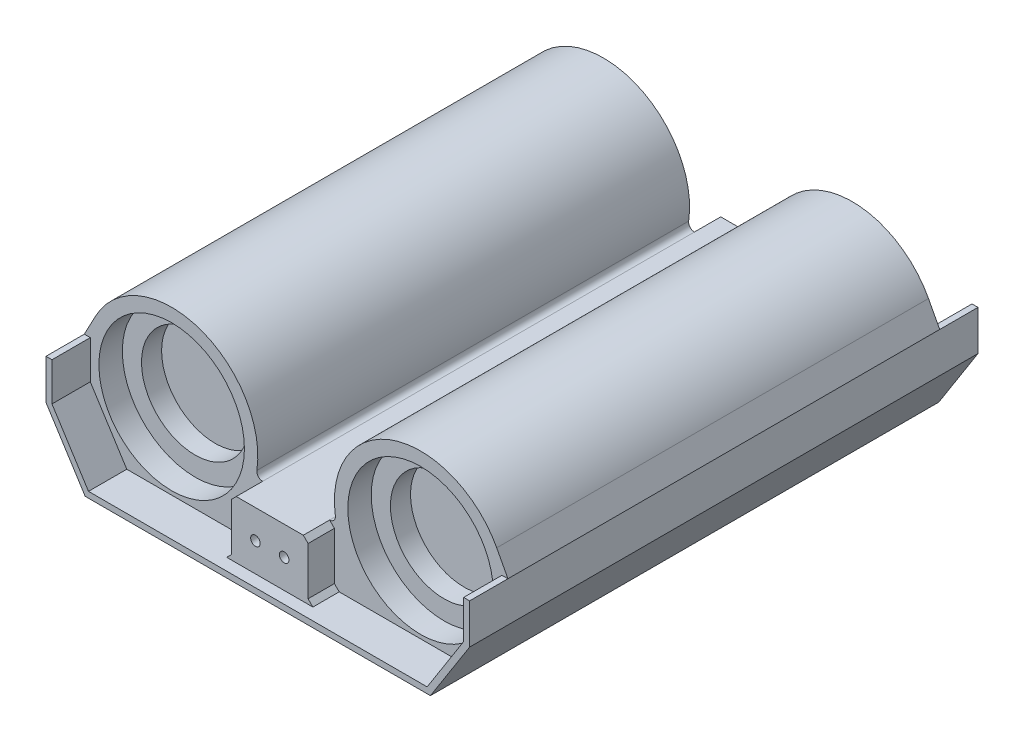
SolidWorks part; units mm, degrees
ref_plane "Front Plane" through (0, 0, 0) normal (0, 0, 1) x (1, 0, 0)
ref_plane "Top Plane" through (0, 0, 0) normal (0, 1, 0) x (1, 0, 0)
ref_plane "Right Plane" through (0, 0, 0) normal (1, 0, 0) x (0, 0, -1)
sketch "Sketch3" plane through (0, 0, 0) normal (0, 0, 1) x (1, 0, 0)
  line L0 (-7.5, -25) -> (7.5, -25) construction
  line L3 (-20, -10) -> (20, -10)
  line L4 (-20, -40) -> (-20, -10)
  line L5 (-20, -40) -> (20, -40)
  line L6 (20, -40) -> (20, -10)
  line L7 (0, -40) -> (0, -10) construction
  line L8 (0, -10) -> (0, 0) construction
  circle A2 centre (7.5, -25) radius 2.5
  circle A3 centre (-7.5, -25) radius 2.5
  point P11 (0, -25)
  dimension "D4" = 5
  dimension "D5" = 5
  dimension "D1" = 15
  dimension "D2" = 40
  dimension "D3" = 30
  dimension "D6" = 15
  dimension "D7" = 10
extrude "Boss-Extrude2" add sketch "Sketch3" along normal blind 6.25
sketch "Sketch4" plane through (0, 0, 6.25) normal (0, 0, 1) x (1, 0, 0)
  line L0 (20, -40) -> (20, -10) construction
  line L1 (-20, -40) -> (20, -40)
  line L2 (-20, -40) -> (-20, -33.75)
  line L3 (-20, -33.75) -> (20, -33.75)
  line L4 (20, -40) -> (20, -33.75)
  dimension "D1" = 6.25
extrude "Boss-Extrude3" add sketch "Sketch4" along normal blind 7.5
sketch "Sketch5" plane through (0, 0, 13.75) normal (0, 0, 1) x (1, 0, 0)
  line L1 (-20, -40) -> (-88.4287, -40)
  line L12 (-110.625, -10.9092) -> (-90.1451, -43.125)
  line L13 (0, -33.75) -> (0, -40) construction
  line L27 (-107.5, -10) -> (-88.4287, -40)
  line L29 (-107.5, 10) -> (-107.5, -10)
  line L30 (-107.5, 10) -> (-110.625, 10)
  line L31 (-110.625, 10) -> (-110.625, -10.9092)
  line L32 (110.625, 10) -> (110.625, -10.9092)
  line L33 (107.5, 10) -> (110.625, 10)
  line L34 (107.5, 10) -> (107.5, -10)
  line L35 (107.5, -10) -> (88.4287, -40)
  line L36 (110.625, -10.9092) -> (90.1451, -43.125)
  line L38 (20, -40) -> (88.4287, -40)
  line L39 (-90.1451, -43.125) -> (90.1451, -43.125)
  line L40 (-20, -40) -> (20, -40) construction
  line L41 (-20, -40) -> (20, -40)
  arc A1 (-104.9218, -10.3078) -> (-55, -40) centre (-65, 0) ccw construction
  arc A4 (104.9218, -10.3078) -> (55, -40) centre (65, 0) cw construction
  dimension "D3" = 3.125
  dimension "D2" = 3.125
  dimension "D4" = 3.125
  dimension "D7" = 20
  dimension "D1" = 10
  dimension "D5" = 42.5
  dimension "D6" = 50
  dimension "D8" = 65
extrude "Boss-Extrude4" add sketch "Sketch5" against normal blind 20
chamfer "Chamfer1" distance 2.5 angle 45 4 edges at (-20, -10, 3.125) (20, -10, 3.125) (-20, -40, 6.875) (20, -40, 6.875)
sketch "Sketch6" plane through (0, 0, 13.75) normal (0, 0, 1) x (1, 0, 0)
  line L0 (-110.625, 10) -> (-104.7676, 21.0604)
  line L1 (-90.1451, -43.125) -> (90.1451, -43.125) construction
  line L2 (-110.625, -10.9092) -> (-90.1451, -43.125) construction
  line L3 (-110.625, 10) -> (-110.625, -10.9092) construction
  line L4 (-90.1451, -43.125) -> (90.1451, -43.125)
  line L5 (-110.625, -10.9092) -> (-90.1451, -43.125)
  line L6 (-110.625, 10) -> (-110.625, -10.9092)
  line L7 (0, 0) -> (0, -43.125) construction
  line L9 (-65, 0) -> (0, 0) construction
  line L11 (17.5, -10) -> (-17.5, -10)
  line L15 (110.625, 10) -> (110.625, -10.9092)
  line L16 (110.625, -10.9092) -> (90.1451, -43.125)
  line L17 (110.625, 10) -> (104.7676, 21.0604)
  circle A1 centre (-65, 0) radius 38
  arc A3 (-20.4793, -6.5503) -> (-104.7676, 21.0604) centre (-65, 0) ccw
  arc A5 (-20.4793, -6.5503) -> (-17.5, -10) centre (-17.5, -6.9886) ccw
  arc A6 (20.4793, -6.5503) -> (17.5, -10) centre (17.5, -6.9886) cw
  arc A7 (20.4793, -6.5503) -> (104.7676, 21.0604) centre (65, 0) cw
  circle A8 centre (65, 0) radius 38
  point P26 (0, -10)
  dimension "D1" = 76
  dimension "D2" = 65
  dimension "D3" = 45
extrude "Boss-Extrude5" add sketch "Sketch6" along normal blind 12.25
sketch "Sketch8" plane through (0, 0, 26) normal (0, 0, 1) x (1, 0, 0)
  line L0 (-65, 0) -> (0, 0) construction
  line L1 (0, 0) -> (0, -43.125) construction
  line L2 (-90.1451, -43.125) -> (90.1451, -43.125) construction
  line L13 (-104.7676, 21.0604) -> (-110.625, 10)
  line L14 (-110.625, 10) -> (-110.625, -10.9092)
  line L15 (-110.625, -10.9092) -> (-90.1451, -43.125)
  line L16 (-90.1451, -43.125) -> (90.1451, -43.125)
  line L17 (90.1451, -43.125) -> (110.625, -10.9092)
  line L18 (110.625, -10.9092) -> (110.625, 10)
  line L19 (110.625, 10) -> (104.7676, 21.0604)
  line L21 (17.5, -10) -> (-17.5, -10)
  line L23 (-104.7676, 21.0604) -> (-110.625, 10)
  line L24 (-110.625, 10) -> (-110.625, -10.9092)
  line L25 (-110.625, -10.9092) -> (-90.1451, -43.125)
  line L26 (-90.1451, -43.125) -> (90.1451, -43.125)
  line L27 (90.1451, -43.125) -> (110.625, -10.9092)
  line L28 (110.625, -10.9092) -> (110.625, 10)
  line L29 (110.625, 10) -> (104.7676, 21.0604)
  line L31 (17.5, -10) -> (-17.5, -10)
  circle A0 centre (-65, 0) radius 28
  circle A1 centre (65, 0) radius 28
  arc A5 (-20.4793, -6.5503) -> (-104.7676, 21.0604) centre (-65, 0) ccw
  arc A6 (104.7676, 21.0604) -> (20.4793, -6.5503) centre (65, 0) ccw
  arc A7 (17.5, -10) -> (20.4793, -6.5503) centre (17.5, -6.9886) ccw
  arc A8 (-20.4793, -6.5503) -> (-17.5, -10) centre (-17.5, -6.9886) ccw
  arc A9 (-20.4793, -6.5503) -> (-104.7676, 21.0604) centre (-65, 0) ccw
  arc A10 (104.7676, 21.0604) -> (20.4793, -6.5503) centre (65, 0) ccw
  arc A11 (17.5, -10) -> (20.4793, -6.5503) centre (17.5, -6.9886) ccw
  arc A12 (-20.4793, -6.5503) -> (-17.5, -10) centre (-17.5, -6.9886) ccw
  dimension "D1" = 56
  dimension "D2" = 0
extrude "Boss-Extrude7" add sketch "Sketch8" along normal blind 10.5
sketch "Sketch9" plane through (0, 0, 36.5) normal (0, 0, 1) x (1, 0, 0)
  line L0 (0, 0) -> (0, -43.125) construction
  line L1 (-90.1451, -43.125) -> (90.1451, -43.125) construction
  circle A2 centre (65, 0) radius 31.125
  circle A3 centre (-65, 0) radius 31.125
  circle A4 centre (-65, 0) radius 31.125
  dimension "D1" = 3.125
extrude "Boss-Extrude8" add sketch "Sketch9" along normal blind 3.125
fillet "Fillet1" radius 4 2 edges at (33.875, 0, 36.5) (-33.875, 0, 36.5)
sketch "Sketch10" plane through (0, 0, 36.5) normal (0, 0, 1) x (1, 0, 0)
  line L10 (-104.7676, 21.0604) -> (-110.625, 10)
  line L11 (-110.625, 10) -> (-110.625, -10.9092)
  line L12 (-110.625, -10.9092) -> (-90.1451, -43.125)
  line L13 (-90.1451, -43.125) -> (90.1451, -43.125)
  line L14 (90.1451, -43.125) -> (110.625, -10.9092)
  line L15 (110.625, -10.9092) -> (110.625, 10)
  line L16 (110.625, 10) -> (104.7676, 21.0604)
  line L18 (17.5, -10) -> (-17.5, -10)
  line L20 (-104.7676, 21.0604) -> (-110.625, 10)
  line L21 (-110.625, 10) -> (-110.625, -10.9092)
  line L22 (-110.625, -10.9092) -> (-90.1451, -43.125)
  line L23 (-90.1451, -43.125) -> (-47.5, -43.125)
  line L24 (90.1451, -43.125) -> (110.625, -10.9092)
  line L25 (110.625, -10.9092) -> (110.625, 10)
  line L26 (110.625, 10) -> (104.7676, 21.0604)
  line L28 (17.5, -10) -> (-17.5, -10)
  line L30 (-47.5, -43.125) -> (-47.5, -40)
  line L31 (47.5, -43.125) -> (47.5, -40)
  line L32 (47.5, -43.125) -> (90.1451, -43.125)
  line L33 (47.5, -40) -> (88.4287, -40)
  line L40 (-102.006, 19.5978) -> (-107.5, 9.2236)
  line L41 (-107.5, 9.2236) -> (-107.5, -10)
  line L42 (-107.5, -10) -> (-88.4287, -40)
  line L43 (-88.4287, -40) -> (88.4287, -40)
  line L44 (88.4287, -40) -> (107.5, -10)
  line L45 (107.5, -10) -> (107.5, 9.2236)
  line L46 (107.5, 9.2236) -> (102.006, 19.5978)
  line L48 (17.5, -13.125) -> (-17.5, -13.125)
  line L50 (-102.006, 19.5978) -> (-107.5, 9.2236)
  line L51 (-107.5, 9.2236) -> (-107.5, -10)
  line L52 (-107.5, -10) -> (-88.4287, -40)
  line L53 (-88.4287, -40) -> (-47.5, -40)
  line L54 (88.4287, -40) -> (107.5, -10)
  line L55 (107.5, -10) -> (107.5, 9.2236)
  line L56 (107.5, 9.2236) -> (102.006, 19.5978)
  line L58 (17.5, -13.125) -> (-17.5, -13.125)
  arc A4 (-20.4793, -6.5503) -> (-104.7676, 21.0604) centre (-65, 0) ccw
  arc A5 (104.7676, 21.0604) -> (20.4793, -6.5503) centre (65, 0) ccw
  arc A6 (17.5, -10) -> (20.4793, -6.5503) centre (17.5, -6.9886) ccw
  arc A7 (-20.4793, -6.5503) -> (-17.5, -10) centre (-17.5, -6.9886) ccw
  arc A8 (-20.4793, -6.5503) -> (-104.7676, 21.0604) centre (-65, 0) ccw
  arc A9 (104.7676, 21.0604) -> (20.4793, -6.5503) centre (65, 0) ccw
  arc A10 (17.5, -10) -> (20.4793, -6.5503) centre (17.5, -6.9886) ccw
  arc A11 (-20.4793, -6.5503) -> (-17.5, -10) centre (-17.5, -6.9886) ccw
  arc A16 (-23.571, -6.0954) -> (-102.006, 19.5978) centre (-65, 0) ccw
  arc A17 (102.006, 19.5978) -> (23.571, -6.0954) centre (65, 0) ccw
  arc A18 (17.5, -13.125) -> (23.571, -6.0954) centre (17.5, -6.9886) ccw
  arc A19 (-23.571, -6.0954) -> (-17.5, -13.125) centre (-17.5, -6.9886) ccw
  arc A20 (-23.571, -6.0954) -> (-102.006, 19.5978) centre (-65, 0) ccw
  arc A21 (102.006, 19.5978) -> (23.571, -6.0954) centre (65, 0) ccw
  arc A22 (17.5, -13.125) -> (23.571, -6.0954) centre (17.5, -6.9886) ccw
  arc A23 (-23.571, -6.0954) -> (-17.5, -13.125) centre (-17.5, -6.9886) ccw
  dimension "D3" = 47.5
  dimension "D4" = 47.5
  dimension "D1" = 0
  dimension "D2" = 3.125
extrude "Boss-Extrude9" add sketch "Sketch10" along normal blind 90
mirror "Mirror1" about plane through (-65, 0, 126.5) normal (0, 0, 1) of "Boss-Extrude2", "Boss-Extrude3", "Boss-Extrude4", "Chamfer1", "Boss-Extrude5", "Boss-Extrude7", "Boss-Extrude8", "Fillet1", "Boss-Extrude9"
ref_plane "Plane1" through (0, 0, 126.5) normal (0, 0, -1) x (-1, 0, 0)
sketch "Sketch12" plane through (0, 0, 253) normal (0, 0, 1) x (1, 0, 0)
  line L8 (-20, -12.5) -> (-20, -37.5)
  line L9 (-20, -37.5) -> (-22.5, -40)
  line L10 (-22.5, -40) -> (22.5, -40)
  line L11 (22.5, -40) -> (20, -37.5)
  line L12 (20, -37.5) -> (20, -12.5)
  line L13 (20, -12.5) -> (17.5, -10)
  line L14 (17.5, -10) -> (-17.5, -10)
  line L15 (-17.5, -10) -> (-20, -12.5)
  line L16 (-20, -12.5) -> (-20, -37.5)
  line L17 (-20, -37.5) -> (-22.5, -40)
  line L18 (-22.5, -40) -> (22.5, -40)
  line L19 (22.5, -40) -> (20, -37.5)
  line L20 (20, -37.5) -> (20, -12.5)
  line L21 (20, -12.5) -> (17.5, -10)
  line L22 (17.5, -10) -> (-17.5, -10)
  line L23 (-17.5, -10) -> (-20, -12.5)
  circle A0 centre (7.5, -25) radius 2.5 construction
  circle A1 centre (-7.5, -25) radius 2.5 construction
  circle A2 centre (7.5, -25) radius 2.5
  circle A3 centre (-7.5, -25) radius 2.5
  dimension "D1" = 0
extrude "Boss-Extrude10" add sketch "Sketch12" against normal blind 30
mirror "Mirror2" about plane through (0, 0, 126.5) normal (0, 0, -1) of "Boss-Extrude10"
sketch "Sketch13" plane through (0, 0, 0) normal (1, 0, 0) x (0, 0, -1)
  line L0 (-216.5, -43.125) -> (-41.5, -43.125)
  line L1 (-36.5, -38.125) -> (-36.5, -25.2895)
  line L2 (-36.5, 35.0281) -> (-36.5, -35.0281) construction
  line L3 (-41.5, -20.2895) -> (-126.5, -20.2895)
  arc A0 (-36.5, -25.2895) -> (-41.5, -20.2895) centre (-41.5, -25.2895) ccw
  arc A1 (-41.5, -43.125) -> (-36.5, -38.125) centre (-41.5, -38.125) ccw
  point P10 (-36.5, -20.2895)
  point P13 (-36.5, -43.125)
  dimension "D1" = 5
equation "\"a\"=3.125"
equation "\"D3@Sketch5\"=\"a\""
equation "\"D2@Sketch5\"=\"a\""
equation "\"D4@Sketch5\"=\"a\""
